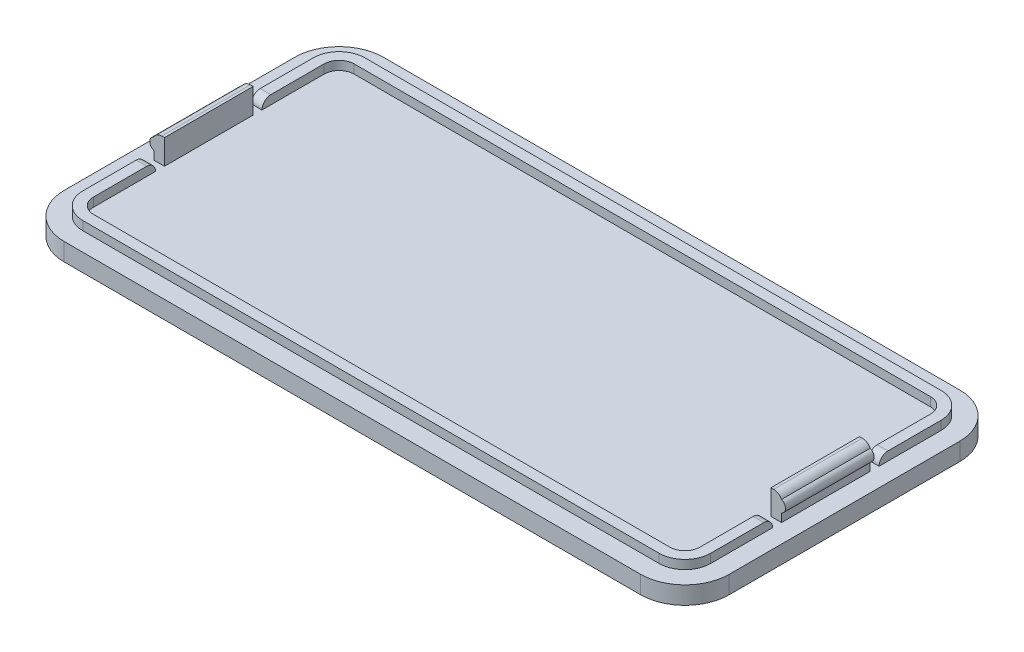
SolidWorks part; units mm, degrees
ref_plane "前视基准面" through (0, 0, 0) normal (0, 0, 1) x (1, 0, 0)
ref_plane "上视基准面" through (0, 0, 0) normal (0, 1, 0) x (1, 0, 0)
ref_plane "右视基准面" through (0, 0, 0) normal (1, 0, 0) x (0, 0, -1)
sketch "zero" plane through (0, 0, 0) normal (0, 1, 0) x (1, 0, 0)
  line L1 (-29.5, 15) -> (29.5, 15)
  line L2 (-32.5, 12) -> (-32.5, -12)
  line L3 (-29.5, -15) -> (29.5, -15)
  line L4 (32.5, 12) -> (32.5, -12)
  line L5 (-32.5, 15) -> (32.5, -15) construction
  line L6 (-32.5, -15) -> (32.5, 15) construction
  line L7 (-25.7, -15) -> (-14.5, -15)
  line L8 (-25.7, -15) -> (-25.7, -9.6569)
  line L9 (-25.7, -9.6569) -> (-14.5, -9.6569)
  line L10 (-14.5, -15) -> (-14.5, -9.6569)
  line L11 (5.2, -15) -> (12.7, -15)
  line L12 (5.2, -15) -> (5.2, -11)
  line L13 (5.2, -11) -> (12.7, -11)
  line L14 (12.7, -15) -> (12.7, -11)
  line L15 (17.8, -15) -> (25.3, -15)
  line L16 (17.8, -15) -> (17.8, -11)
  line L17 (17.8, -11) -> (25.3, -11)
  line L18 (25.3, -15) -> (25.3, -11)
  line L19 (-32.5, 7.7) -> (-19.5, 7.7)
  line L20 (-32.5, 7.7) -> (-32.5, -4.3)
  line L21 (-32.5, -4.3) -> (-19.5, -4.3)
  line L22 (-19.5, 7.7) -> (-19.5, -4.3)
  line L23 (-25.5, 14) -> (25.5, 14)
  line L24 (-25.5, 14) -> (-25.5, 8.8)
  line L25 (-25.5, 8.8) -> (25.5, 8.8)
  line L26 (25.5, 14) -> (25.5, 8.8)
  line L27 (-19.5, 7.2329) -> (-35.5, 7.2329)
  line L28 (-19.5, 7.2329) -> (-19.5, -3.7671)
  line L29 (-19.5, -3.7671) -> (-35.5, -3.7671)
  line L30 (-35.5, 7.2329) -> (-35.5, -3.7671)
  arc A0 (29.5, -15) -> (32.5, -12) centre (29.5, -12) ccw
  arc A1 (29.5, 15) -> (32.5, 12) centre (29.5, 12) cw
  arc A2 (-32.5, -12) -> (-29.5, -15) centre (-29.5, -12) ccw
  arc A3 (-29.5, 15) -> (-32.5, 12) centre (-29.5, 12) ccw
  circle A4 centre (-29, 11.4) radius 3
  circle A5 centre (-29, -11.5) radius 3
  circle A6 centre (29, 11.4) radius 3
  circle A7 centre (29, -11.5) radius 3
  circle A8 centre (-29, 11.4) radius 1.375
  circle A9 centre (-29, -11.5) radius 1.375
  circle A10 centre (29, -11.5) radius 1.375
  circle A11 centre (29, 11.4) radius 1.375
  point P0 (0, 0)
  dimension "D3" = 3
  dimension "D4" = 6
  dimension "D9" = 2.75
  dimension "D1" = 65
  dimension "D2" = 30
  dimension "D5" = 3.6
  dimension "D6" = 3.5
  dimension "D7" = 3.5
  dimension "D8" = 3.5
  dimension "D10" = 12
  dimension "D11" = 7.3
  dimension "D12" = 13
  dimension "D13" = 11.2
  dimension "D14" = 6.8
  dimension "D15" = 19.7
  dimension "D16" = 7.5
  dimension "D17" = 7.5
  dimension "D18" = 5.1
  dimension "D19" = 4
  dimension "D20" = 5.2
  dimension "D21" = 7
  dimension "D22" = 7
  dimension "D23" = 1
  dimension "D24" = 11
  dimension "D25" = 16
sketch "sugar" plane through (0, 0, 0) normal (0, 1, 0) x (1, 0, 0)
  line L1 (-29.5, 15) -> (29.5, 15)
  line L2 (-32.5, 12) -> (-32.5, -12)
  line L3 (-29.5, -15) -> (29.5, -15)
  line L4 (32.5, 12) -> (32.5, -12)
  line L5 (-32.5, 15) -> (32.5, -15) construction
  line L6 (-32.5, -15) -> (32.5, 15) construction
  line L7 (23.5, -11.5) -> (19.5, -11.5)
  line L8 (23.5, -11.5) -> (23.5, -13.9082)
  line L9 (23.5, -13.9082) -> (19.5, -13.9082)
  line L10 (19.5, -11.5) -> (19.5, -13.9082)
  line L11 (16, -11.0071) -> (8.5, -11.0071)
  line L12 (16, -11.0071) -> (16, -15)
  line L13 (16, -15) -> (8.5, -15)
  line L14 (8.5, -11.0071) -> (8.5, -15)
  line L15 (20.5, -13.9082) -> (22.5, -13.9082)
  line L16 (20.5, -13.9082) -> (20.5, -14.8173)
  line L17 (20.5, -14.8173) -> (22.5, -14.8173)
  line L18 (22.5, -13.9082) -> (22.5, -14.8173)
  arc A0 (29.5, 15) -> (32.5, 12) centre (29.5, 12) cw
  arc A1 (29.5, -15) -> (32.5, -12) centre (29.5, -12) ccw
  arc A2 (-32.5, -12) -> (-29.5, -15) centre (-29.5, -12) ccw
  arc A3 (-29.5, 15) -> (-32.5, 12) centre (-29.5, 12) ccw
  circle A4 centre (-29, 11.4) radius 3
  circle A5 centre (-29, 11.4) radius 1.375
  circle A6 centre (-29, -11.5) radius 3
  circle A7 centre (-29, -11.5) radius 1.375
  circle A8 centre (29, 11.4) radius 3
  circle A9 centre (29, 11.4) radius 1.375
  circle A10 centre (29, -11.5) radius 3
  circle A11 centre (29, -11.5) radius 1.375
  dimension "D3" = 3
  dimension "D1" = 65
  dimension "D2" = 30
  dimension "D4" = 9
  dimension "D5" = 4
  dimension "D6" = 3.5
  dimension "D7" = 7.5
  dimension "D8" = 2
  dimension "D9" = 1
sketch "case" plane through (0, 0, 0) normal (0, 1, 0) x (1, 0, 0)
  line L1 (-34.0422, 18) -> (30.9578, 18)
  line L2 (-39.0422, 13) -> (-39.0422, -13)
  line L3 (-34.0422, -18) -> (30.9578, -18)
  line L4 (35.9578, 13) -> (35.9578, -13)
  line L5 (-39.0422, 18) -> (35.9578, -18) construction
  line L6 (-39.0422, -18) -> (35.9578, 18) construction
  arc A0 (-39.0422, -13) -> (-34.0422, -18) centre (-34.0422, -13) ccw
  arc A1 (30.9578, -18) -> (35.9578, -13) centre (30.9578, -13) ccw
  arc A2 (30.9578, 18) -> (35.9578, 13) centre (30.9578, 13) cw
  arc A3 (-34.0422, 18) -> (-39.0422, 13) centre (-34.0422, 13) ccw
  point P0 (-1.5422, 0)
  point P3 (-1.5422, 0)
  dimension "D3" = 5
  dimension "D1" = 75
  dimension "D2" = 36
extrude "凸台-拉伸2" add sketch "case" along normal blind 2
sketch "草图2" plane through (0, 0, 0) normal (0, 1, 0) x (1, 0, 0)
  line L4 (-34.0422, -14.7) -> (30.9578, -14.7)
  line L5 (32.6578, -13) -> (32.6578, 13)
  line L6 (30.9578, 14.7) -> (-34.0422, 14.7)
  line L7 (-35.7422, 13) -> (-35.7422, -13)
  line L8 (33.8578, -13) -> (33.8578, 13)
  line L9 (30.9578, 15.9) -> (-34.0422, 15.9)
  line L10 (-36.9422, 13) -> (-36.9422, -13)
  line L11 (-34.0422, -15.9) -> (30.9578, -15.9)
  line L12 (33.8578, -13) -> (33.8578, 13)
  line L13 (30.9578, 15.9) -> (-34.0422, 15.9)
  line L14 (-36.9422, 13) -> (-36.9422, -13)
  line L15 (-34.0422, -15.9) -> (30.9578, -15.9)
  arc A4 (30.9578, -14.7) -> (32.6578, -13) centre (30.9578, -13) ccw
  arc A5 (32.6578, 13) -> (30.9578, 14.7) centre (30.9578, 13) ccw
  arc A6 (-34.0422, 14.7) -> (-35.7422, 13) centre (-34.0422, 13) ccw
  arc A7 (-35.7422, -13) -> (-34.0422, -14.7) centre (-34.0422, -13) ccw
  arc A8 (30.9578, -15.9) -> (33.8578, -13) centre (30.9578, -13) ccw
  arc A9 (33.8578, 13) -> (30.9578, 15.9) centre (30.9578, 13) ccw
  arc A10 (-34.0422, 15.9) -> (-36.9422, 13) centre (-34.0422, 13) ccw
  arc A11 (-36.9422, -13) -> (-34.0422, -15.9) centre (-34.0422, -13) ccw
  arc A12 (30.9578, -15.9) -> (33.8578, -13) centre (30.9578, -13) ccw
  arc A13 (33.8578, 13) -> (30.9578, 15.9) centre (30.9578, 13) ccw
  arc A14 (-34.0422, 15.9) -> (-36.9422, 13) centre (-34.0422, 13) ccw
  arc A15 (-36.9422, -13) -> (-34.0422, -15.9) centre (-34.0422, -13) ccw
  dimension "D1" = 2.1
  dimension "D2" = 1.2
ref_plane "基准面1" through (0, 2, 0) normal (0, 1, 0) x (1, 0, 0)
sketch "草图3" plane through (0, 2, 0) normal (0, 1, 0) x (1, 0, 0)
  line L4 (-34.0422, -14.7) -> (30.9578, -14.7)
  line L5 (32.6578, -13) -> (32.6578, 13)
  line L6 (30.9578, 14.7) -> (-34.0422, 14.7)
  line L7 (-35.7422, 13) -> (-35.7422, -13)
  line L8 (-34.0422, -14.7) -> (30.9578, -14.7)
  line L9 (32.6578, -13) -> (32.6578, 13)
  line L10 (30.9578, 14.7) -> (-34.0422, 14.7)
  line L11 (-35.7422, 13) -> (-35.7422, -13)
  line L12 (-36.9422, 13) -> (-36.9422, -13)
  line L13 (-34.0422, -15.9) -> (30.9578, -15.9)
  line L14 (33.8578, -13) -> (33.8578, 13)
  line L15 (30.9578, 15.9) -> (-34.0422, 15.9)
  line L16 (-36.9422, 13) -> (-36.9422, -13)
  line L17 (-34.0422, -15.9) -> (30.9578, -15.9)
  line L18 (33.8578, -13) -> (33.8578, 13)
  line L19 (30.9578, 15.9) -> (-34.0422, 15.9)
  arc A4 (30.9578, -14.7) -> (32.6578, -13) centre (30.9578, -13) ccw
  arc A5 (32.6578, 13) -> (30.9578, 14.7) centre (30.9578, 13) ccw
  arc A6 (-34.0422, 14.7) -> (-35.7422, 13) centre (-34.0422, 13) ccw
  arc A7 (-35.7422, -13) -> (-34.0422, -14.7) centre (-34.0422, -13) ccw
  arc A8 (30.9578, -14.7) -> (32.6578, -13) centre (30.9578, -13) ccw
  arc A9 (32.6578, 13) -> (30.9578, 14.7) centre (30.9578, 13) ccw
  arc A10 (-34.0422, 14.7) -> (-35.7422, 13) centre (-34.0422, 13) ccw
  arc A11 (-35.7422, -13) -> (-34.0422, -14.7) centre (-34.0422, -13) ccw
  arc A12 (-36.9422, -13) -> (-34.0422, -15.9) centre (-34.0422, -13) ccw
  arc A13 (30.9578, -15.9) -> (33.8578, -13) centre (30.9578, -13) ccw
  arc A14 (33.8578, 13) -> (30.9578, 15.9) centre (30.9578, 13) ccw
  arc A15 (-34.0422, 15.9) -> (-36.9422, 13) centre (-34.0422, 13) ccw
  arc A16 (-36.9422, -13) -> (-34.0422, -15.9) centre (-34.0422, -13) ccw
  arc A17 (30.9578, -15.9) -> (33.8578, -13) centre (30.9578, -13) ccw
  arc A18 (33.8578, 13) -> (30.9578, 15.9) centre (30.9578, 13) ccw
  arc A19 (-34.0422, 15.9) -> (-36.9422, 13) centre (-34.0422, 13) ccw
  dimension "D1" = 0
  dimension "D2" = 0
extrude "凸台-拉伸4" add sketch "草图3" along normal blind 1
ref_plane "基准面3" through (33.8578, 0, 0) normal (1, 0, 0) x (0, 0, -1)
sketch "草图7" plane through (0, 2, 0) normal (0, 1, 0) x (1, 0, 0)
  line L0 (-36.9422, 13) -> (-36.9422, -13) construction
  line L1 (-36.9422, 5) -> (-35.7422, 5)
  line L2 (-36.9422, 5) -> (-36.9422, -5)
  line L3 (-36.9422, -5) -> (-35.7422, -5)
  line L4 (-35.7422, 5) -> (-35.7422, -5)
  line L5 (-35.7422, 13) -> (-35.7422, -13) construction
  point P10 (-35.7422, 0)
  dimension "D1" = 5
  dimension "D2" = 10
extrude "凸台-拉伸8" add sketch "草图7" along normal blind 2.8
ref_plane "基准面5" through (0, 0, 5) normal (0, 0, 1) x (1, 0, 0)
sketch "草图8" plane through (0, 0, 5) normal (0, 0, 1) x (1, 0, 0)
  line L0 (-34.0422, 2) -> (-39.0422, 2) construction
  line L1 (-36.9422, 4.8) -> (-36.9422, 3) construction
  circle A0 centre (-36.6922, 3.6) radius 0.7
  dimension "D1" = 1.4
  dimension "D2" = 1.6
  dimension "D3" = 0.25
extrude "凸台-拉伸9" add sketch "草图8" against normal blind 10
fillet "圆角1" radius 1 1 edges at (-36.9422, 4.8, 0)
ref_plane "基准面7" through (-36.9422, 0, 0) normal (-1, 0, 0) x (0, 0, 1)
sketch "草图11" plane through (-36.9422, 0, 0) normal (-1, 0, 0) x (0, 0, 1)
  line L0 (-13, 2) -> (13, 2) construction
  line L1 (5, 3) -> (6, 3)
  line L2 (5, 3) -> (5, 2)
  line L3 (5, 2) -> (6, 2)
  line L4 (6, 3) -> (6, 2)
  line L6 (-5, 3) -> (-6, 3)
  line L7 (-5, 3) -> (-5, 2)
  line L8 (-5, 2) -> (-6, 2)
  line L9 (-6, 3) -> (-6, 2)
  dimension "D1" = 1
  dimension "D2" = 1
extrude "切除-拉伸1" cut sketch "草图11" against normal blind 1.2
fillet "圆角2" radius 1 2 edges at (-36.3422, 3, 6) (-36.3422, 3, -6)
ref_plane "基准面8" through (0, 0, 0) normal (0, -1, 0) x (-1, 0, 0)
sketch "草图12" plane through (0, 0, 0) normal (0, -1, 0) x (-1, 0, 0)
  line L76 (34.0422, -18) -> (-30.9578, -18) construction
  line L78 (39.0422, 13) -> (39.0422, -13) construction
  line B0 (-8.1993, 5.026) -> (-9.0198, 5.499)
  line B1 (-9.0198, 5.499) -> (-13.2767, 7.9551)
  line B2 (-13.2767, 7.9551) -> (-14.0973, 8.4339)
  line B3 (-15.8183, 8.4339) -> (-16.6389, 7.9551)
  line B4 (-16.6389, 7.9551) -> (-20.8958, 5.499)
  line B5 (-20.8958, 5.499) -> (-21.7165, 5.026)
  line B6 (-22.577, 3.5387) -> (-22.577, -3.2769)
  line B7 (-21.7165, -4.7643) -> (-20.8958, -5.2373)
  line B8 (-20.8958, -5.2373) -> (-16.6389, -7.6934)
  line B9 (-16.6389, -7.6934) -> (-15.8183, -8.172)
  line B10 (-14.0973, -8.172) -> (-13.2767, -7.6934)
  line B11 (-13.2767, -7.6934) -> (-9.0198, -5.2373)
  line B12 (-9.0198, -5.2373) -> (-8.1993, -4.7643)
  line B13 (-7.3388, -3.2769) -> (-7.3388, 3.5387)
  line B14 (-20.6223, 4.3479) -> (-15.3568, 7.391)
  line B15 (-14.5532, 7.391) -> (-9.3162, 4.3422)
  line B16 (-9.3105, 3.6413) -> (-14.3993, 0.5982)
  line B17 (-12.8208, -4.5591) -> (-13.4135, -4.8896)
  line B18 (-13.4705, -4.9865) -> (-13.4705, -6.6961)
  line B19 (-13.5274, -6.793) -> (-14.633, -7.4198)
  line B20 (-14.7983, -7.3229) -> (-14.7983, -2.046)
  line B21 (-14.7413, -1.9491) -> (-12.8607, -0.8835)
  line B22 (-8.9173, -4.2058) -> (-10.0114, -4.8269)
  line B23 (-10.1767, -4.7301) -> (-10.1767, -2.2169)
  line B24 (-10.1197, -2.1201) -> (-9.0256, -1.5046)
  line B25 (-8.8603, -1.6015) -> (-8.8603, -4.1089)
  line B26 (-12.8893, -3.5447) -> (-13.4135, -3.8069)
  line B27 (-13.4705, -3.6872) -> (-13.4705, -2.3423)
  line B28 (-13.4135, -2.2455) -> (-12.9234, -1.9719)
  line B29 (-3.344, 3.06) -> (-5.2189, 3.06)
  line B30 (-5.2189, 3.06) -> (-5.2189, -3.5048)
  line B31 (-5.2189, -3.5048) -> (-4.3868, -3.5048)
  line B32 (-4.3868, -3.5048) -> (-4.3868, -0.9005)
  line B33 (-4.3868, -0.9005) -> (-3.2984, -0.9005)
  line B34 (-3.4066, -0.2281) -> (-4.3868, -0.2281)
  line B35 (-4.3868, -0.2281) -> (-4.3868, 2.3876)
  line B36 (-4.3868, 2.3876) -> (-3.4408, 2.3876)
  line B37 (0.1948, 1.3618) -> (0.1948, -3.5048)
  line B38 (0.1948, -3.5048) -> (1.0098, -3.5048)
  line B39 (1.0098, -3.5048) -> (1.0098, 1.3618)
  line B40 (1.0098, 1.3618) -> (0.1948, 1.3618)
  line B41 (5.7169, 0.2847) -> (4.8849, 0.6153)
  line B42 (6.0417, 1.4017) -> (6.8396, 2.4047)
  line B43 (3.6084, -0.5586) -> (4.4575, -0.9177)
  line B44 (2.9074, -1.5673) -> (2.0014, -2.6729)
  line B45 (10.8229, 1.5898) -> (10.8229, -1.7497)
  line B46 (9.3811, -1.3621) -> (9.3811, 1.5898)
  line B47 (9.3811, 1.5898) -> (7.7912, 1.5898)
  line B48 (7.7912, 1.5898) -> (7.7912, -1.5616)
  line B49 (10.9711, -2.8039) -> (11.0052, -2.8039)
  line B50 (11.0052, -2.8039) -> (11.1193, -3.5048)
  line B51 (11.1193, -3.5048) -> (12.4185, -3.5048)
  line B52 (12.4185, -3.5048) -> (12.4185, 1.5898)
  line B53 (12.4185, 1.5898) -> (10.8229, 1.5898)
  line B54 (16.2708, -2.5019) -> (15.4673, -2.5019)
  line B55 (17.365, 0.4386) -> (18.1513, 0.4386)
  line B56 (18.1513, 0.4386) -> (18.1513, 1.5898)
  line B57 (18.1513, 1.5898) -> (16.2822, 1.5898)
  line B58 (14.0312, -1.4533) -> (14.0312, -1.4875)
  line B59 (13.9344, -3.3168) -> (13.9344, -3.3624)
  line B60 (15.4844, -3.7214) -> (15.9688, -3.7214)
  line B61 (18.6072, 1.0484) -> (19.1657, -0.0002)
  line B62 (21.411, -2.992) -> (21.4508, -2.992)
  line B63 (21.4508, -2.992) -> (21.5648, -3.5048)
  line B64 (21.5648, -3.5048) -> (22.8641, -3.5048)
  line B65 (22.8641, -3.5048) -> (22.8641, -0.6099)
  line B66 (21.2685, -1.1741) -> (21.2685, -1.989)
  line B67 (25.3545, 0.7065) -> (25.3203, 0.7065)
  line B68 (25.3203, 0.7065) -> (25.212, 1.5898)
  line B69 (25.212, 1.5898) -> (23.9127, 1.5898)
  line B70 (23.9127, 1.5898) -> (23.9127, -3.5048)
  line B71 (23.9127, -3.5048) -> (25.4969, -3.5048)
  line B72 (25.4969, -3.5048) -> (25.4969, -0.5928)
  line B73 (27.1552, 0.2392) -> (27.423, 1.6125)
  line B74 (-13.4135, -3.8069) -> (-13.4135, -4.8896)
  line B75 (-13.4705, -3.6872) -> (-13.4705, -4.9865)
  spline B76 degree 3 poles (-14.0973, 8.4339) (-14.3652, 8.582) (-14.6615, 8.6618) (-14.9578, 8.6618) knots 3 3 3 3 4 4 4 4
  spline B77 degree 3 poles (-14.9578, 8.6618) (-15.2541, 8.6618) (-15.5505, 8.582) (-15.8183, 8.4339) knots 4 4 4 4 5 5 5 5
  spline B78 degree 3 poles (-21.7165, 5.026) (-22.2464, 4.7183) (-22.577, 4.1485) (-22.577, 3.5387) knots 8 8 8 8 9 9 9 9
  spline B79 degree 3 poles (-22.577, -3.2769) (-22.577, -3.8923) (-22.2464, -4.4565) (-21.7165, -4.7643) knots 10 10 10 10 11 11 11 11
  spline B80 degree 3 poles (-15.8183, -8.172) (-15.5505, -8.3259) (-15.2541, -8.4) (-14.9578, -8.4) knots 14 14 14 14 15 15 15 15
  spline B81 degree 3 poles (-14.9578, -8.4) (-14.6615, -8.4) (-14.3652, -8.3259) (-14.0973, -8.172) knots 15 15 15 15 16 16 16 16
  spline B82 degree 3 poles (-8.1993, -4.7643) (-7.6636, -4.4565) (-7.3388, -3.8923) (-7.3388, -3.2769) knots 19 19 19 19 20 20 20 20
  spline B83 degree 3 poles (-7.3388, 3.5387) (-7.3388, 4.1485) (-7.6636, 4.7183) (-8.1993, 5.026) knots 21 21 21 21 22 22 22 22
  spline B84 degree 2 poles (-15.5106, 0.5982) (-20.6622, 3.5729) (-20.6736, 3.5786) knots 0 0 0 1 1 1
  spline B85 degree 3 poles (-20.6736, 3.5786) (-20.9414, 3.7723) (-20.9129, 4.1826) (-20.6223, 4.3479) knots 1 1 1 1 2 2 2 2
  spline B86 degree 3 poles (-15.3568, 7.391) (-15.1117, 7.5335) (-14.8039, 7.5335) (-14.5532, 7.391) knots 3 3 3 3 4 4 4 4
  spline B87 degree 3 poles (-9.3162, 4.3422) (-9.0484, 4.1883) (-9.0427, 3.8008) (-9.3105, 3.6413) knots 5 5 5 5 6 6 6 6
  spline B88 degree 3 poles (-14.3993, 0.5982) (-14.7413, 0.3987) (-15.1687, 0.3987) (-15.5106, 0.5982) knots 7 7 7 7 8 8 8 8
  spline B89 degree 3 poles (-13.4705, -6.6961) (-13.4705, -6.736) (-13.4876, -6.7702) (-13.5274, -6.793) knots 3 3 3 3 4 4 4 4
  spline B90 degree 3 poles (-14.633, -7.4198) (-14.7071, -7.4597) (-14.7983, -7.4084) (-14.7983, -7.3229) knots 5 5 5 5 6 6 6 6
  spline B91 degree 3 poles (-14.7983, -2.046) (-14.7983, -2.0061) (-14.7812, -1.9662) (-14.7413, -1.9491) knots 7 7 7 7 8 8 8 8
  spline B92 degree 3 poles (-12.8607, -0.8835) (-11.6412, -0.1939) (-10.6326, -0.0572) (-10.6326, -1.4249) knots 9 9 9 9 10 10 10 10
  spline B93 degree 3 poles (-10.6326, -1.4249) (-10.6326, -2.7412) (-11.6526, -3.898) (-12.8208, -4.5591) knots 10 10 10 10 11 11 11 11
  spline B94 degree 3 poles (-8.8603, -4.1089) (-8.8603, -4.1488) (-8.8831, -4.1887) (-8.9173, -4.2058) knots 0 0 0 0 1 1 1 1
  spline B95 degree 3 poles (-10.0114, -4.8269) (-10.0855, -4.8668) (-10.1767, -4.8155) (-10.1767, -4.7301) knots 2 2 2 2 3 3 3 3
  spline B96 degree 3 poles (-10.1767, -2.2169) (-10.1767, -2.1771) (-10.1539, -2.1429) (-10.1197, -2.1201) knots 4 4 4 4 5 5 5 5
  spline B97 degree 3 poles (-9.0256, -1.5046) (-8.9515, -1.4647) (-8.8603, -1.516) (-8.8603, -1.6015) knots 6 6 6 6 7 7 7 7
  spline B98 degree 3 poles (-9.5156, 0.1651) (-9.0768, 0.4158) (-8.7634, 0.3076) (-8.7634, -0.0914) (-8.7634, -0.4846) (-9.0768, -0.9461) (-9.5156, -1.1912) knots 2 2 2 2 3 3 3 4 4 4 4
  spline B99 degree 3 poles (-9.5156, -1.1912) (-9.9601, -1.4476) (-10.2735, -1.3394) (-10.2735, -0.9461) (-10.2735, -0.5415) (-9.9601, -0.0856) (-9.5156, 0.1651) knots 0 0 0 0 1 1 1 2 2 2 2
  spline B100 degree 3 poles (-11.9319, -2.16) (-11.9319, -2.7013) (-12.2395, -3.18) (-12.8893, -3.5447) knots 0 0 0 0 1 1 1 1
  spline B101 degree 3 poles (-13.4705, -2.3423) (-13.4705, -2.3024) (-13.4477, -2.2625) (-13.4135, -2.2455) knots 4 4 4 4 5 5 5 5
  spline B102 degree 3 poles (-12.9234, -1.9719) (-12.2852, -1.6072) (-11.9319, -1.6015) (-11.9319, -2.16) knots 6 6 6 6 7 7 7 7
  spline B103 degree 3 poles (-3.2984, -0.9005) (-1.868, -0.9005) (-0.8822, -0.2509) (-0.8822, 1.1339) knots 5 5 5 5 6 6 6 6
  spline B104 degree 3 poles (-0.8822, 1.1339) (-0.8822, 2.5699) (-1.868, 3.06) (-3.344, 3.06) knots 6 6 6 6 7 7 7 7
  spline B105 degree 3 poles (-3.4408, 2.3876) (-2.2897, 2.3876) (-1.7084, 2.0855) (-1.7084, 1.1339) knots 3 3 3 3 4 4 4 4
  spline B106 degree 3 poles (-1.7084, 1.1339) (-1.7084, 0.1936) (-2.2498, -0.2281) (-3.4066, -0.2281) knots 4 4 4 4 5 5 5 5
  spline B107 degree 3 poles (0.6052, 2.3648) (0.93, 2.3648) (1.1694, 2.587) (1.1694, 2.889) (1.1694, 3.2253) (0.93, 3.419) (0.6052, 3.419) knots 2 2 2 2 3 3 3 4 4 4 4
  spline B108 degree 3 poles (0.6052, 3.419) (0.2804, 3.419) (0.041, 3.2253) (0.041, 2.889) (0.041, 2.587) (0.2804, 2.3648) (0.6052, 2.3648) knots 0 0 0 0 1 1 1 2 2 2 2
  spline B109 degree 3 poles (4.8849, 0.6153) (4.2979, 0.8489) (3.8762, 0.9914) (3.8762, 1.3618) knots 1 1 1 1 2 2 2 2
  spline B110 degree 3 poles (3.8762, 1.3618) (3.8762, 1.7151) (4.1783, 1.9146) (4.674, 1.9146) knots 2 2 2 2 3 3 3 3
  spline B111 degree 3 poles (4.674, 1.9146) (5.1926, 1.9146) (5.6029, 1.7379) (6.0417, 1.4017) knots 3 3 3 3 4 4 4 4
  spline B112 degree 3 poles (6.8396, 2.4047) (6.2583, 2.9916) (5.4433, 3.2879) (4.674, 3.2879) knots 5 5 5 5 6 6 6 6
  spline B113 degree 3 poles (4.674, 3.2879) (3.2551, 3.2879) (2.2521, 2.3876) (2.2521, 1.2706) knots 6 6 6 6 7 7 7 7
  spline B114 degree 3 poles (2.2521, 1.2706) (2.2521, 0.3019) (2.9074, -0.2794) (3.6084, -0.5586) knots 7 7 7 7 8 8 8 8
  spline B115 degree 3 poles (4.4575, -0.9177) (5.0274, -1.157) (5.3978, -1.2824) (5.3978, -1.6699) knots 9 9 9 9 10 10 10 10
  spline B116 degree 3 poles (5.3978, -1.6699) (5.3978, -2.0289) (5.1185, -2.2511) (4.5259, -2.2511) knots 10 10 10 10 11 11 11 11
  spline B117 degree 3 poles (4.5259, -2.2511) (4.0016, -2.2511) (3.3804, -1.9719) (2.9074, -1.5673) knots 11 11 11 11 12 12 12 12
  spline B118 degree 3 poles (2.0014, -2.6729) (2.6909, -3.3054) (3.6254, -3.6302) (4.4916, -3.6302) knots 13 13 13 13 14 14 14 14
  spline B119 degree 3 poles (4.4916, -3.6302) (6.1044, -3.6302) (7.0389, -2.6557) (7.0389, -1.5445) knots 14 14 14 14 15 15 15 15
  spline B120 degree 3 poles (7.0389, -1.5445) (7.0389, -0.6042) (6.5432, -0.0458) (5.7169, 0.2847) knots 15 15 15 15 16 16 16 16
  spline B121 degree 3 poles (10.8229, -1.7497) (10.5551, -2.1258) (10.3328, -2.2682) (9.9738, -2.2682) knots 1 1 1 1 2 2 2 2
  spline B122 degree 3 poles (9.9738, -2.2682) (9.5692, -2.2682) (9.3811, -2.0688) (9.3811, -1.3621) knots 2 2 2 2 3 3 3 3
  spline B123 degree 3 poles (7.7912, -1.5616) (7.7912, -2.8324) (8.2642, -3.6302) (9.3754, -3.6302) knots 6 6 6 6 7 7 7 7
  spline B124 degree 3 poles (9.3754, -3.6302) (10.0706, -3.6302) (10.5494, -3.3054) (10.9711, -2.8039) knots 7 7 7 7 8 8 8 8
  spline B125 degree 3 poles (15.4673, -2.5019) (14.9202, -2.5019) (14.7151, -2.3936) (14.7151, -2.16) knots 1 1 1 1 2 2 2 2
  spline B126 degree 3 poles (14.7151, -2.16) (14.7151, -1.989) (14.7549, -1.9092) (14.8746, -1.8009) knots 2 2 2 2 3 3 3 3
  spline B127 degree 3 poles (14.8746, -1.8009) (15.0969, -1.8636) (15.302, -1.8921) (15.473, -1.8921) knots 3 3 3 3 4 4 4 4
  spline B128 degree 3 poles (15.473, -1.8921) (16.6013, -1.8921) (17.5074, -1.3735) (17.5074, -0.1825) knots 4 4 4 4 5 5 5 5
  spline B129 degree 3 poles (17.5074, -0.1825) (17.5074, 0.0625) (17.4447, 0.2962) (17.365, 0.4386) knots 5 5 5 5 6 6 6 6
  spline B130 degree 3 poles (16.2822, 1.5898) (16.0485, 1.6752) (15.7693, 1.7151) (15.473, 1.7151) knots 9 9 9 9 10 10 10 10
  spline B131 degree 3 poles (15.473, 1.7151) (14.3732, 1.7151) (13.3417, 1.1111) (13.3417, -0.1369) knots 10 10 10 10 11 11 11 11
  spline B132 degree 3 poles (13.3417, -0.1369) (13.3417, -0.7296) (13.6722, -1.2026) (14.0312, -1.4533) knots 11 11 11 11 12 12 12 12
  spline B133 degree 3 poles (14.0312, -1.4875) (13.7007, -1.7212) (13.467, -2.0802) (13.467, -2.4392) knots 13 13 13 13 14 14 14 14
  spline B134 degree 3 poles (13.467, -2.4392) (13.467, -2.8666) (13.6665, -3.1344) (13.9344, -3.3168) knots 14 14 14 14 15 15 15 15
  spline B135 degree 3 poles (13.9344, -3.3624) (13.4613, -3.6017) (13.2106, -3.9436) (13.2106, -4.3653) knots 16 16 16 16 17 17 17 17
  spline B136 degree 3 poles (13.2106, -4.3653) (13.2106, -5.2771) (14.1737, -5.6475) (15.3476, -5.6475) knots 17 17 17 17 18 18 18 18
  spline B137 degree 3 poles (15.3476, -5.6475) (17.1199, -5.6475) (18.2312, -4.8839) (18.2312, -3.8069) knots 18 18 18 18 19 19 19 19
  spline B138 degree 3 poles (18.2312, -3.8069) (18.2312, -2.8837) (17.5245, -2.5019) (16.2708, -2.5019) knots 19 19 19 19 20 20 20 20
  spline B139 degree 3 poles (15.473, -0.9347) (15.1083, -0.9347) (14.8291, -0.6669) (14.8291, -0.1369) (14.8291, 0.3816) (15.1083, 0.6495) (15.473, 0.6495) knots 2 2 2 2 3 3 3 4 4 4 4
  spline B140 degree 3 poles (15.473, 0.6495) (15.8491, 0.6495) (16.1169, 0.3816) (16.1169, -0.1369) (16.1169, -0.6669) (15.8491, -0.9347) (15.473, -0.9347) knots 0 0 0 0 1 1 1 2 2 2 2
  spline B141 degree 3 poles (15.5983, -4.6503) (14.943, -4.6503) (14.5156, -4.4736) (14.5156, -4.1146) knots 0 0 0 0 1 1 1 1
  spline B142 degree 3 poles (14.5156, -4.1146) (14.5156, -3.9436) (14.5953, -3.8012) (14.7549, -3.6587) knots 1 1 1 1 2 2 2 2
  spline B143 degree 3 poles (14.7549, -3.6587) (14.9202, -3.7043) (15.114, -3.7214) (15.4844, -3.7214) knots 2 2 2 2 3 3 3 3
  spline B144 degree 3 poles (15.9688, -3.7214) (16.4417, -3.7214) (16.7096, -3.7841) (16.7096, -4.0861) knots 4 4 4 4 5 5 5 5
  spline B145 degree 3 poles (16.7096, -4.0861) (16.7096, -4.4109) (16.2537, -4.6503) (15.5983, -4.6503) knots 5 5 5 5 6 6 6 6
  spline B146 degree 3 poles (20.8013, 1.7151) (20.0091, 1.7151) (19.2797, 1.4473) (18.6072, 1.0484) knots 0 0 0 0 1 1 1 1
  spline B147 degree 3 poles (19.1657, -0.0002) (19.6729, 0.2847) (20.0946, 0.4443) (20.4992, 0.4443) knots 2 2 2 2 3 3 3 3
  spline B148 degree 3 poles (20.4992, 0.4443) (21.0177, 0.4443) (21.2344, 0.205) (21.2685, -0.2053) knots 3 3 3 3 4 4 4 4
  spline B149 degree 3 poles (21.2685, -0.2053) (19.2797, -0.4219) (18.4362, -1.0031) (18.4362, -2.0802) knots 4 4 4 4 5 5 5 5
  spline B150 degree 3 poles (18.4362, -2.0802) (18.4362, -2.9293) (19.0118, -3.6302) (19.9522, -3.6302) knots 5 5 5 5 6 6 6 6
  spline B151 degree 3 poles (19.9522, -3.6302) (20.5163, -3.6302) (20.9893, -3.3681) (21.411, -2.992) knots 6 6 6 6 7 7 7 7
  spline B152 degree 3 poles (22.8641, -0.6099) (22.8641, 0.9857) (22.1176, 1.7151) (20.8013, 1.7151) knots 11 11 11 11 12 12 12 12
  spline B153 degree 3 poles (21.2685, -1.989) (21.0349, -2.2398) (20.824, -2.3936) (20.4992, -2.3936) knots 0 0 0 0 1 1 1 1
  spline B154 degree 3 poles (20.4992, -2.3936) (20.1686, -2.3936) (19.9522, -2.2511) (19.9522, -1.9548) knots 1 1 1 1 2 2 2 2
  spline B155 degree 3 poles (19.9522, -1.9548) (19.9522, -1.5958) (20.277, -1.3109) (21.2685, -1.1741) knots 2 2 2 2 3 3 3 3
  spline B156 degree 3 poles (26.8076, 1.7151) (26.2947, 1.7151) (25.7305, 1.3846) (25.3545, 0.7065) knots 0 0 0 0 1 1 1 1
  spline B157 degree 3 poles (25.4969, -0.5928) (25.7648, 0.0796) (26.2207, 0.3189) (26.5967, 0.3189) knots 7 7 7 7 8 8 8 8
  spline B158 degree 3 poles (26.5967, 0.3189) (26.8247, 0.3189) (26.9729, 0.2847) (27.1552, 0.2392) knots 8 8 8 8 9 9 9 9
  spline B159 degree 3 poles (27.423, 1.6125) (27.2806, 1.6752) (27.1096, 1.7151) (26.8076, 1.7151) knots 10 10 10 10 11 11 11 11
  dimension "D1" = 9.6
  dimension "D2" = 54
sketch_block_instance "块1-1"
sketch_block "块1"
extrude "切除-拉伸2" cut sketch "草图12" against normal blind 0.5
sketch "草图13" plane through (0, 3, 0) normal (0, 1, 0) x (1, 0, 0)
  line L0 (32.6578, -13) -> (32.6578, 13) construction
  line L1 (32.6578, 5) -> (33.8578, 5)
  line L2 (32.6578, 5) -> (32.6578, -5)
  line L3 (32.6578, -5) -> (33.8578, -5)
  line L4 (33.8578, 5) -> (33.8578, -5)
  line L5 (33.8578, -13) -> (33.8578, 13) construction
  line L7 (35.9578, -13) -> (35.9578, 13) construction
  point P12 (35.9578, 0)
  point P13 (33.8578, 0)
  dimension "D1" = 10
extrude "凸台-拉伸10" add sketch "草图13" along normal blind 1.8
sketch "草图14" plane through (0, 0, 5) normal (0, 0, 1) x (1, 0, 0)
  line L0 (33.8578, 2) -> (30.9578, 2) construction
  line L1 (33.8578, 4.8) -> (33.8578, 3) construction
  circle A0 centre (33.6078, 3.6) radius 0.7
  dimension "D2" = 1.4
  dimension "D1" = 1.6
  dimension "D3" = 0.25
extrude "凸台-拉伸11" add sketch "草图14" against normal blind 10
fillet "圆角3" radius 1 1 edges at (33.8578, 4.8, 0)
sketch "草图15" plane through (0, 3, 0) normal (0, 1, 0) x (1, 0, 0)
  line L0 (33.8578, 5) -> (33.8578, 13) construction
  line L1 (32.6578, 5) -> (33.8578, 5)
  line L2 (32.6578, 5) -> (32.6578, 6)
  line L3 (32.6578, 6) -> (33.8578, 6)
  line L4 (33.8578, 5) -> (33.8578, 6)
  line L5 (33.8578, -13) -> (33.8578, -5) construction
  line L6 (32.6578, -5) -> (33.8578, -5)
  line L7 (32.6578, -5) -> (32.6578, -6)
  line L8 (32.6578, -6) -> (33.8578, -6)
  line L9 (33.8578, -5) -> (33.8578, -6)
  dimension "D1" = 1
  dimension "D2" = 1
extrude "切除-拉伸3" cut sketch "草图15" against normal blind 1
fillet "圆角4" radius 1 2 edges at (33.2578, 3, 6) (33.2578, 3, -6)
